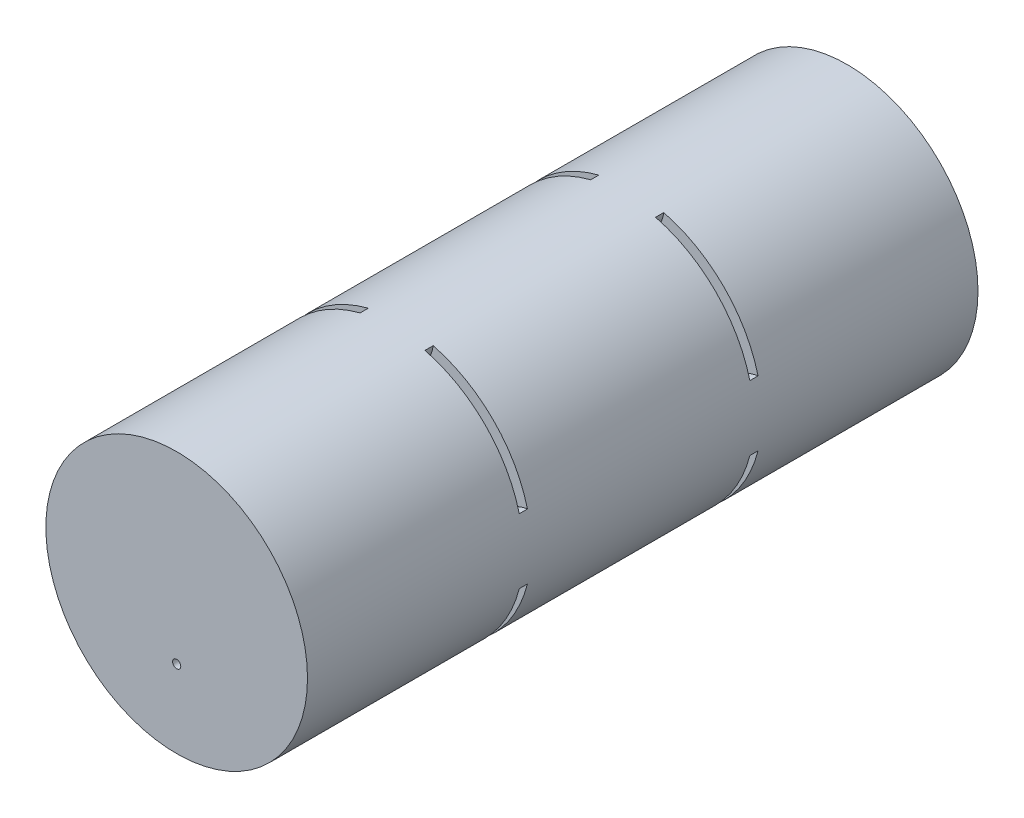
SolidWorks part; units mm, degrees
material "Water"
ref_plane "Front Plane" through (0, 0, 0) normal (0, 0, 1) x (1, 0, 0)
ref_plane "Top Plane" through (0, 0, 0) normal (0, 1, 0) x (1, 0, 0)
ref_plane "Right Plane" through (0, 0, 0) normal (1, 0, 0) x (0, 0, -1)
sketch "Sketch1" plane through (0, 0, 0) normal (0, 0, 1) x (1, 0, 0)
  circle A0 centre (0, 0) radius 50.8
  dimension "D1" = 101.6
extrude "Boss-Extrude1" add sketch "Sketch1" along normal blind 260.35
sketch "Sketch2" plane through (0, 0, 260.35) normal (0, 0, 1) x (1, 0, 0)
  circle A0 centre (0, 50.8) radius 12.7 construction
  circle A1 centre (0, 0) radius 50.8 construction
  circle A2 centre (0, 0) radius 19.05
  circle A3 centre (50.8, 0) radius 12.7 construction
  circle A4 centre (0, -50.8) radius 12.7 construction
  circle A5 centre (-50.8, 0) radius 12.7 construction
  arc A6 (-12.6004, 49.2125) -> (-49.2125, 12.6004) centre (0, 0) ccw
  arc A7 (-49.2125, 12.6004) -> (-49.2125, -12.6004) centre (-50.8, 0) cw
  arc A8 (12.6004, 49.2125) -> (-12.6004, 49.2125) centre (0, 50.8) cw
  arc A9 (49.2125, 12.6004) -> (12.6004, 49.2125) centre (0, 0) ccw
  arc A10 (49.2125, -12.6004) -> (49.2125, 12.6004) centre (50.8, 0) cw
  arc A11 (12.6004, -49.2125) -> (49.2125, -12.6004) centre (0, 0) ccw
  arc A12 (-12.6004, -49.2125) -> (12.6004, -49.2125) centre (0, -50.8) cw
  arc A13 (-49.2125, -12.6004) -> (-12.6004, -49.2125) centre (0, 0) ccw
  point P16 (0, 0)
  point P32 (0, 0)
  dimension "D1" = 25.4
  dimension "D2" = 38.1
  dimension "D3" = 4
  dimension "D4" = 4
extrude "Cut-Extrude1" cut sketch "Sketch2" against normal blind 3.175 from offset 83.82 offset against normal yes
sketch "Sketch3" plane through (0, 0, 260.35) normal (0, 0, 1) x (1, 0, 0)
  line L0 (0, 0) -> (0, -50.8) construction
  circle A0 centre (0, 0) radius 19.05 construction
  circle A1 centre (0, 0) radius 50.8 construction
  circle A2 centre (0, -20.6375) radius 1.5875
  dimension "D1" = 38.1
  dimension "D2" = 3.175
extrude "Cut-Extrude2" cut sketch "Sketch3" against normal up to next
ref_plane "Plane1" through (0, 0, 130.175) normal (0, 0, 1) x (1, 0, 0)
mirror "Mirror1" about plane through (0, 0, 130.175) normal (0, 0, 1) of "Cut-Extrude2", "Cut-Extrude1"
